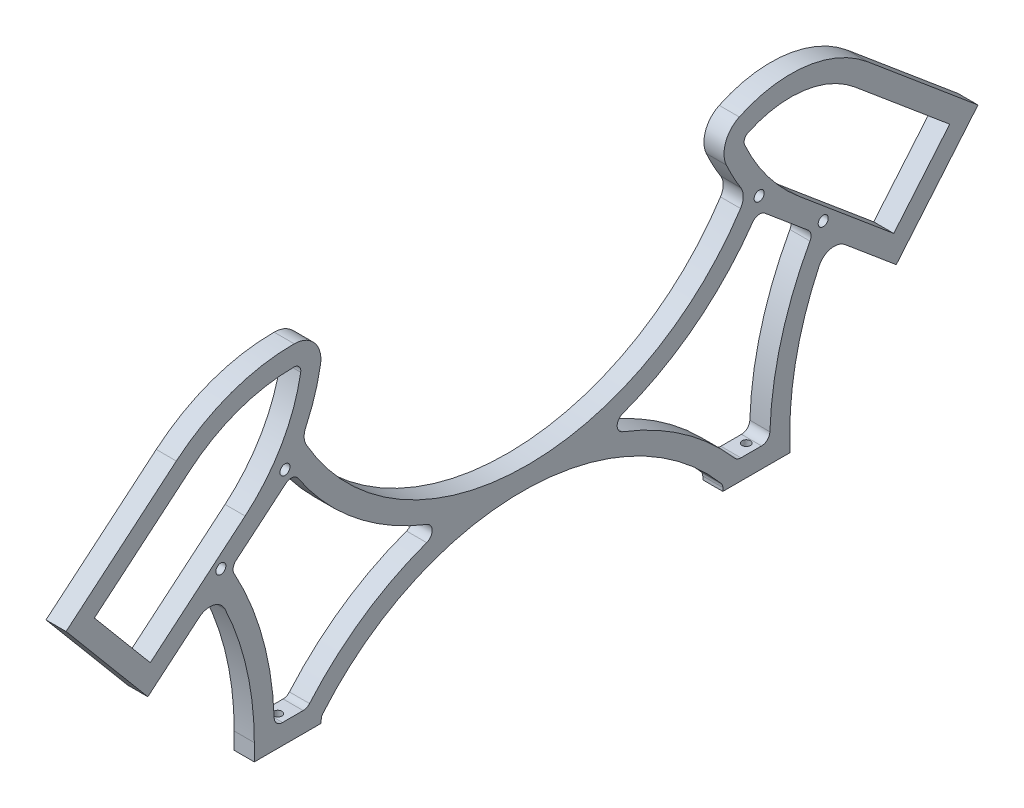
SolidWorks part; units mm, degrees
material "1060 Alloy"
ref_plane "Front Plane" through (0, 0, 0) normal (0, 0, 1) x (1, 0, 0)
ref_plane "Top Plane" through (0, 0, 0) normal (0, 1, 0) x (1, 0, 0)
ref_plane "Right Plane" through (0, 0, 0) normal (1, 0, 0) x (0, 0, -1)
sketch "Sketch1" plane through (0, 0, 0) normal (1, 0, 0) x (0, 0, -1)
  line L0 (0, 0) -> (0, 5)
  line L1 (-55.4789, 62.5279) -> (-29.1246, 31.1201) construction
  line L2 (-55.4789, 62.5279) -> (5.8047, 113.9509) construction
  line L3 (-29.1246, 31.1201) -> (32.1589, 82.5431) construction
  line L4 (-52.0184, 61.5154) -> (-31.4492, 37.0019) construction
  line L5 (5.8047, 113.9509) -> (32.1589, 82.5431) construction
  line L6 (20, 1) -> (20, 0)
  line L7 (0, 0) -> (20, 0)
  line L8 (-31.4492, 37.0019) -> (-0.8075, 62.7135) construction
  line L9 (-21.3767, 87.2269) -> (-52.0184, 61.5154) construction
  line L10 (167.0486, 53.5603) -> (150.4448, 67.4925)
  line L11 (-23.305, 89.525) -> (-56.2449, 61.8851)
  line L12 (11.5903, 69.2002) -> (-7.0486, 53.5603)
  line L13 (154.0052, 6) -> (144.2478, 6)
  line L14 (215.4789, 62.5279) -> (189.1246, 31.1201) construction
  line L15 (215.4789, 62.5279) -> (154.1953, 113.9509) construction
  line L16 (189.1246, 31.1201) -> (127.8411, 82.5431) construction
  line L17 (154.1953, 113.9509) -> (127.8411, 82.5431) construction
  line L18 (191.4492, 37.0019) -> (212.0184, 61.5154) construction
  line L19 (212.0184, 61.5154) -> (181.3767, 87.2269) construction
  line L20 (160.8075, 62.7135) -> (191.4492, 37.0019) construction
  line L21 (201.7338, 49.2587) -> (141.9824, 99.3961) construction
  line L22 (-41.7338, 49.2587) -> (18.0176, 99.3961) construction
  line L23 (15.7522, 6) -> (5.9948, 6)
  line L24 (176.4981, 45.6312) -> (191.819, 32.7755)
  line L25 (191.819, 32.7755) -> (216.2449, 61.8851)
  line L26 (216.2449, 61.8851) -> (183.305, 89.525)
  line L27 (-56.2449, 61.8851) -> (-31.819, 32.7755)
  line L28 (160, 0) -> (160, 5)
  line L29 (-31.819, 32.7755) -> (-16.4981, 45.6312)
  line L30 (-31.819, 32.7755) -> (1.1209, 60.4153) construction
  line L31 (162.7358, 65.0116) -> (191.0795, 41.2284)
  line L32 (191.0795, 41.2284) -> (207.792, 61.1456)
  line L33 (207.792, 61.1456) -> (179.4483, 84.9287)
  line L34 (109.9256, 30) -> (27.8477, 30) construction
  line L35 (109.9256, 36) -> (27.8477, 36) construction
  line L36 (150.0961, 75.6176) -> (170.3963, 58.5837) construction
  line L37 (-19.4483, 84.9287) -> (-47.792, 61.1456)
  line L38 (-47.792, 61.1456) -> (-31.0795, 41.2284)
  line L39 (-31.0795, 41.2284) -> (-2.7358, 65.0116)
  line L40 (158.8791, 60.4153) -> (191.819, 32.7755) construction
  line L41 (150.0961, 75.6176) -> (167.13, 95.9178) construction
  line L42 (170.3963, 58.5837) -> (187.4301, 78.8839) construction
  line L43 (160, 0) -> (140, 0)
  line L44 (167.13, 95.9178) -> (187.4301, 78.8839) construction
  line L56 (140, 1) -> (140, 0)
  line L63 (174.6584, 98) -> (-14.1241, 98) construction
  circle A0 centre (-10, 55) radius 1.5
  circle A1 centre (170, 55) radius 1.5
  circle A2 centre (9.1511, 71.0697) radius 1.5
  circle A3 centre (150.8489, 71.0697) radius 1.5
  circle A4 centre (170, 55) radius 3 construction
  circle A5 centre (150.8489, 71.0697) radius 3 construction
  circle A6 centre (-10, 55) radius 3 construction
  circle A7 centre (9.1511, 71.0697) radius 3 construction
  arc A8 (183.305, 89.525) -> (144.9204, 94.4491) centre (160.2761, 62.0802) ccw
  arc A9 (144.9204, 94.4491) -> (141.0591, 83.9267) centre (148.3493, 87.2212) ccw
  arc A10 (141.0591, 83.9267) -> (145.3352, 75.9601) centre (201.5435, 111.2608) ccw
  arc A11 (15.3664, 78.9036) -> (19.7742, 92.9021) centre (-33.8526, 102.0951) ccw
  arc A12 (-0.8075, 62.7135) -> (16.8174, 93.409) centre (-33.8526, 102.0951) ccw construction
  arc A13 (16.8174, 93.409) -> (11.9131, 99.2537) centre (11.8893, 94.2538) ccw construction
  arc A14 (11.9131, 99.2537) -> (-21.3767, 87.2269) centre (11.6685, 47.8452) ccw construction
  arc A15 (181.3767, 87.2269) -> (146.2062, 91.7387) centre (160.2761, 62.0802) ccw construction
  arc A16 (146.2062, 91.7387) -> (143.7929, 85.1621) centre (148.3493, 87.2212) ccw construction
  arc A17 (143.7929, 85.1621) -> (160.8075, 62.7135) centre (201.5435, 111.2608) ccw construction
  arc A18 (19.7742, 92.9021) -> (11.9273, 102.2537) centre (11.8893, 94.2538) ccw
  arc A19 (11.9273, 102.2537) -> (-23.305, 89.525) centre (11.6685, 47.8452) ccw
  arc A20 (179.4483, 84.9287) -> (147.492, 89.0282) centre (160.2761, 62.0802) ccw
  arc A21 (147.492, 89.0282) -> (146.5267, 86.3976) centre (148.3493, 87.2212) ccw
  arc A22 (146.5267, 86.3976) -> (162.7358, 65.0116) centre (201.5435, 111.2608) ccw
  arc A23 (1.1209, 60.4153) -> (19.7742, 92.9021) centre (-33.8526, 102.0951) ccw construction
  arc A24 (144.2478, 6) -> (102.8723, 32.8181) centre (80, -47.7963) ccw
  arc A25 (58.7004, 33.2478) -> (11.5903, 69.2002) centre (81.5549, 112.0365) cw
  arc A26 (20, 1) -> (20.4696, 2.2876) centre (22, 1) cw
  arc A27 (-2.7358, 65.0116) -> (13.8605, 93.9159) centre (-33.8526, 102.0951) ccw
  arc A28 (13.8605, 93.9159) -> (11.8988, 96.2538) centre (11.8893, 94.2538) ccw
  arc A29 (11.8988, 96.2538) -> (-19.4483, 84.9287) centre (11.6685, 47.8452) ccw
  arc A30 (141.0591, 83.9267) -> (158.8791, 60.4153) centre (201.5435, 111.2608) ccw construction
  arc A31 (150.4448, 67.4925) -> (102.8723, 32.8181) centre (81.5549, 112.0365) cw
  arc A32 (160, 5) -> (168.7665, 43.9435) centre (250.8829, 5) cw
  arc A33 (176.4981, 45.6312) -> (168.7665, 43.9435) centre (173.2842, 41.801) ccw
  arc A34 (0, 5) -> (-8.7665, 43.9435) centre (-90.8829, 5) ccw
  arc A35 (-16.4981, 45.6312) -> (-8.7665, 43.9435) centre (-13.2842, 41.801) cw
  arc A36 (145.3352, 75.9601) -> (145.2922, 70.5744) centre (141.101, 73.3009) cw
  arc A37 (15.3664, 78.9036) -> (15.549, 74.2903) centre (19.8894, 76.7724) ccw
  arc A38 (145.2922, 70.5744) -> (15.549, 74.2903) centre (81.5549, 112.0365) cw
  arc A39 (167.0486, 53.5603) -> (154.0052, 6) centre (250.8829, 5) ccw
  arc A40 (-7.0486, 53.5603) -> (5.9948, 6) centre (-90.8829, 5) cw
  arc A41 (58.7004, 33.2478) -> (15.7522, 6) centre (80, -47.7963) ccw
  arc A42 (144.9204, 94.4491) -> (141.0591, 83.9267) centre (148.3493, 87.2212) ccw construction
  arc A44 (140, 1) -> (139.5304, 2.2876) centre (138, 1) ccw
  arc A45 (139.5304, 2.2876) -> (20.4696, 2.2876) centre (80, -47.7963) ccw
  dimension "D1" = 3
  dimension "D8" = 5
  dimension "D11" = 55
  dimension "D12" = 10
  dimension "D14" = 25
  dimension "D16" = 2
  dimension "D17" = 6
  dimension "D21" = 40
  dimension "D22" = 35
  dimension "D23" = 80
  dimension "D24" = 3
  dimension "D18" = 6
  dimension "D29" = 55
  dimension "D25" = 5
  dimension "D28" = 6
  dimension "D36" = 5
  dimension "D37" = 20
  dimension "D38" = 10
  dimension "D39" = 8
  dimension "D40" = 10
  dimension "D45" = 6
  dimension "D46" = 6
  dimension "D47" = 6
  dimension "D48" = 6
  dimension "D49" = 30
  dimension "D52" = 26.5
  dimension "D53" = 3
  dimension "D56" = 2
  dimension "D4" = 25
  dimension "D6" = 28
  dimension "D7" = 10
  dimension "D9" = 20
  dimension "D10" = 120
  dimension "D13" = 1
  dimension "D15" = 40
  dimension "D19" = 40
  dimension "D20" = 30
  dimension "D26" = 3
  dimension "D27" = 2
  dimension "D30" = 3
  dimension "D31" = 3
  dimension "D32" = 98
  dimension "D33" = 3
  dimension "D34" = 6
  dimension "D35" = 3
  dimension "D41" = 3
  dimension "D42" = 3
  dimension "D43" = 6
  dimension "D44" = 6
  dimension "D50" = 3.5
  dimension "D51" = 26.5
extrude "Boss-Extrude1" add sketch "Sketch1" along normal blind 6
hole_wizard "Tap Drill for M3 Tap1" positions "Sketch3" profile "Sketch2" hole size "M3" standard "ISO"
sketch "Sketch3" plane through (0, 0, 0) normal (0, -1, 0) x (-1, 0, 0)
  line L0 (-6, 20) -> (0, 20) construction
  line L1 (0, 0) -> (0, 20) construction
  line L2 (-6, 140) -> (0, 140) construction
  point P0 (-3, 10)
  point P2 (-3, 150)
  dimension "D1" = 10
  dimension "D2" = 3
  dimension "D3" = 10
sketch "Sketch2" plane through (3, 0, -10) normal (1, 0, 0) x (0, 0, -1)
  line L0 (0, 0) -> (0, 10.7511)
  line L1 (0, 10.7511) -> (1.25, 10)
  line L2 (1.25, 10) -> (1.25, 0)
  line L5 (1.25, 0) -> (0, 0)
  line L10 (0, 10.7511) -> (-1.25, 10) construction
  line L11 (0, -6.35) -> (0, 107.95) construction
  dimension "Hole Dia." = 2.5
  dimension "Hole Depth" = 10
  dimension "Drill Angle" = 118
fillet "Fillet1" radius 2.5 10 edges at (3, 6, -15.7522) (3, 6, -5.9948) (3, 53.5603, 7.0486) (3, 69.2002, -11.5903) (3, 53.5603, -167.0486) (3, 6, -154.0052) (3, 67.4925, -150.4448) (3, 33.2478, -58.7004) (3, 6, -144.2478) (3, 32.8181, -102.8723)
equation "\"ˇ35\"=76.24"
